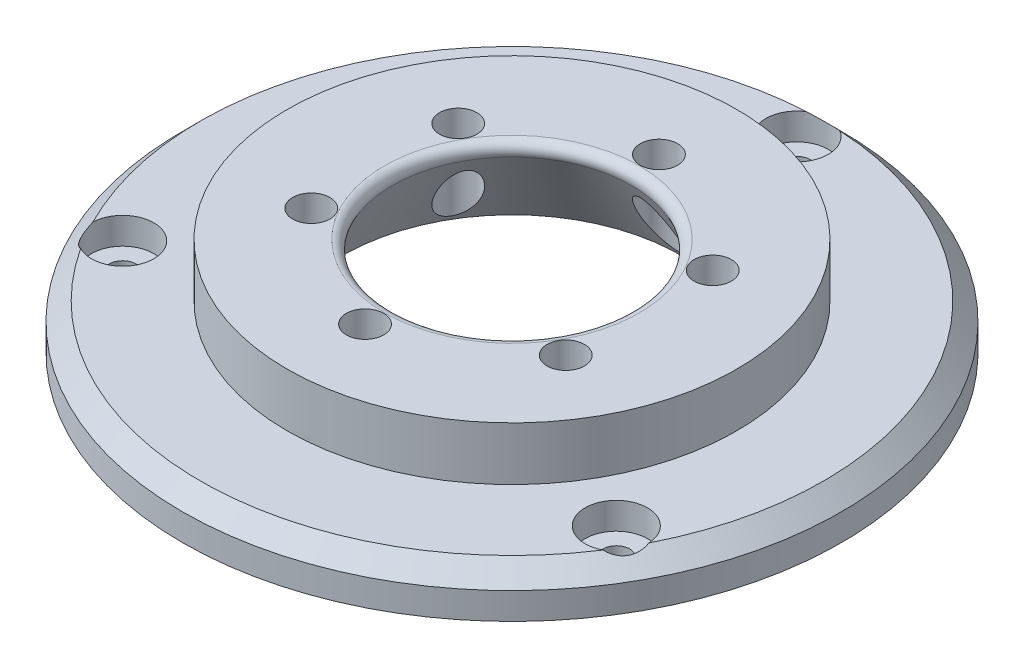
SolidWorks part; units mm, degrees
ref_plane "Front Plane" through (0, 0, 0) normal (0, 0, 1) x (1, 0, 0)
ref_plane "Top Plane" through (0, 0, 0) normal (0, 1, 0) x (1, 0, 0)
ref_plane "Right Plane" through (0, 0, 0) normal (1, 0, 0) x (0, 0, -1)
sketch "Sketch1" plane through (0, 0, 0) normal (0, 1, 0) x (1, 0, 0)
  circle A0 centre (0, 0) radius 25.25
  circle A1 centre (0, 0) radius 12
  dimension "D1" = 50.5
  dimension "D2" = 24
extrude "Boss-Extrude1" add sketch "Sketch1" along normal blind 6
sketch "Sketch2" plane through (0, 0, 0) normal (0, 1, 0) x (1, 0, 0)
  circle A0 centre (0, 0) radius 37
  circle A1 centre (0, 0) radius 12
  circle A2 centre (0, 0) radius 12 construction
  dimension "D1" = 74
extrude "Boss-Extrude2" add sketch "Sketch2" against normal blind 5
sketch "Sketch3" plane through (0, 0, 0) normal (0, 1, 0) x (1, 0, 0)
  circle A0 centre (0, 32) radius 1.5
  dimension "D2" = 3
  dimension "D1" = 32
extrude "Cut-Extrude1" cut sketch "Sketch3" against normal through all
sketch "Sketch4" plane through (0, 0, 0) normal (0, 1, 0) x (1, 0, 0)
  circle A0 centre (0, 32) radius 3.5
  dimension "D1" = 7
extrude "Cut-Extrude2" cut sketch "Sketch4" against normal blind 3 and the other way through all
pattern_circular "CirPattern1" count 3 over 360 about axis through (0, -5, 0) along (0, 1, 0) of "Cut-Extrude1", "Cut-Extrude2"
chamfer "Chamfer1" distance 12 angle 30 1 edges at (0, -5, 12) first distance on face at (0, 6, 12)
chamfer "Chamfer2" distance 2 angle 45 1 edges at (0, 0, 37)
sketch "Sketch5" plane through (0, 6, 0) normal (0, 1, 0) x (1, 0, 0)
  line L0 (0, 16.5) -> (0, 0) construction
  line L1 (0, 0) -> (0, 32) construction
  circle A0 centre (0, 16.5) radius 2.1
  dimension "D2" = 4.2
  dimension "D3" = 16.5
extrude "Cut-Extrude3" cut sketch "Sketch5" against normal through all
pattern_circular "CirPattern2" count 6 over 360 about axis through (0, 6, 0) along (0, -1, 0) of "Cut-Extrude3" reverse direction yes
fillet "Fillet1" radius 1 1 edges at (0, 6, 12.5774)
